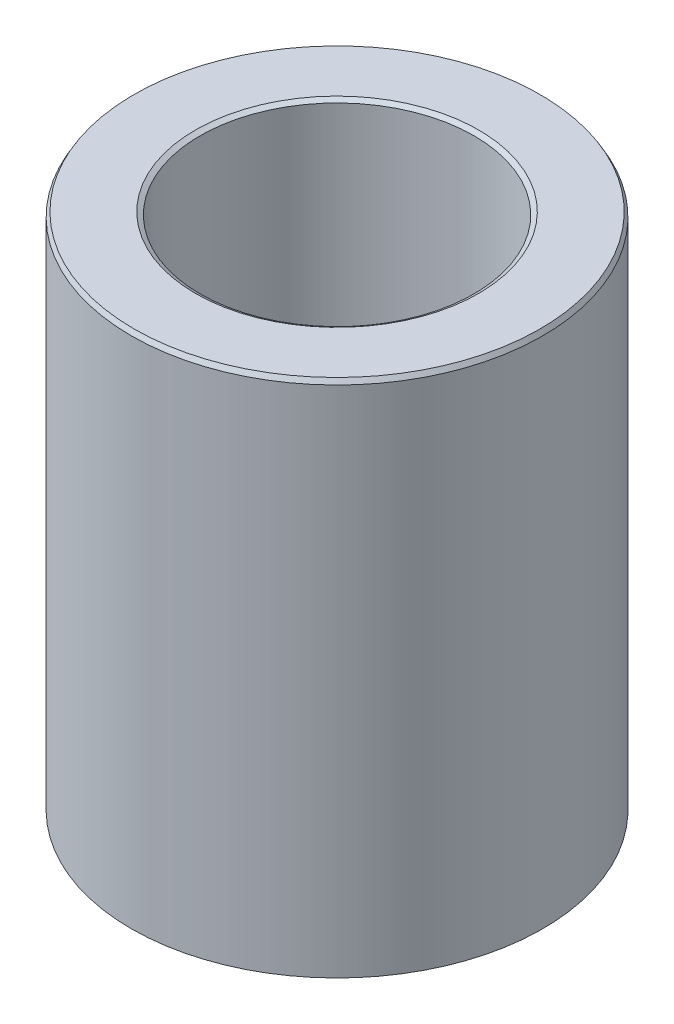
SolidWorks part; units mm, degrees
ref_plane "Front Plane" through (0, 0, 0) normal (0, 0, 1) x (1, 0, 0)
ref_plane "Top Plane" through (0, 0, 0) normal (0, 1, 0) x (1, 0, 0)
ref_plane "Right Plane" through (0, 0, 0) normal (1, 0, 0) x (0, 0, -1)
sketch "Sketch1" plane through (0, 0, 0) normal (0, 1, 0) x (1, 0, 0)
  circle A0 centre (0, 0) radius 40
  dimension "SLEEVE_OD" = 80
extrude "Boss-Extrude1" add sketch "Sketch1" along normal blind 101.2746
sketch "Sketch2" plane through (0, 0, 0) normal (0, 1, 0) x (1, 0, 0)
  circle A0 centre (0, 0) radius 26.6348
  dimension "BORE_D" = 53.2697
extrude "Cut-Extrude1" cut sketch "Sketch2" along normal through all
chamfer "Chamfer1" distance 0.9025 angle 30 4 edges at (0, 101.2746, 26.6348) (0, 0, 26.6348) (0, 0, 40) (0, 101.2746, 40) first distance on face at (0, 101.2746, 26.6348) first distance on face at (0, 0, 26.6348) first distance on face at (0, 101.2746, 40)
